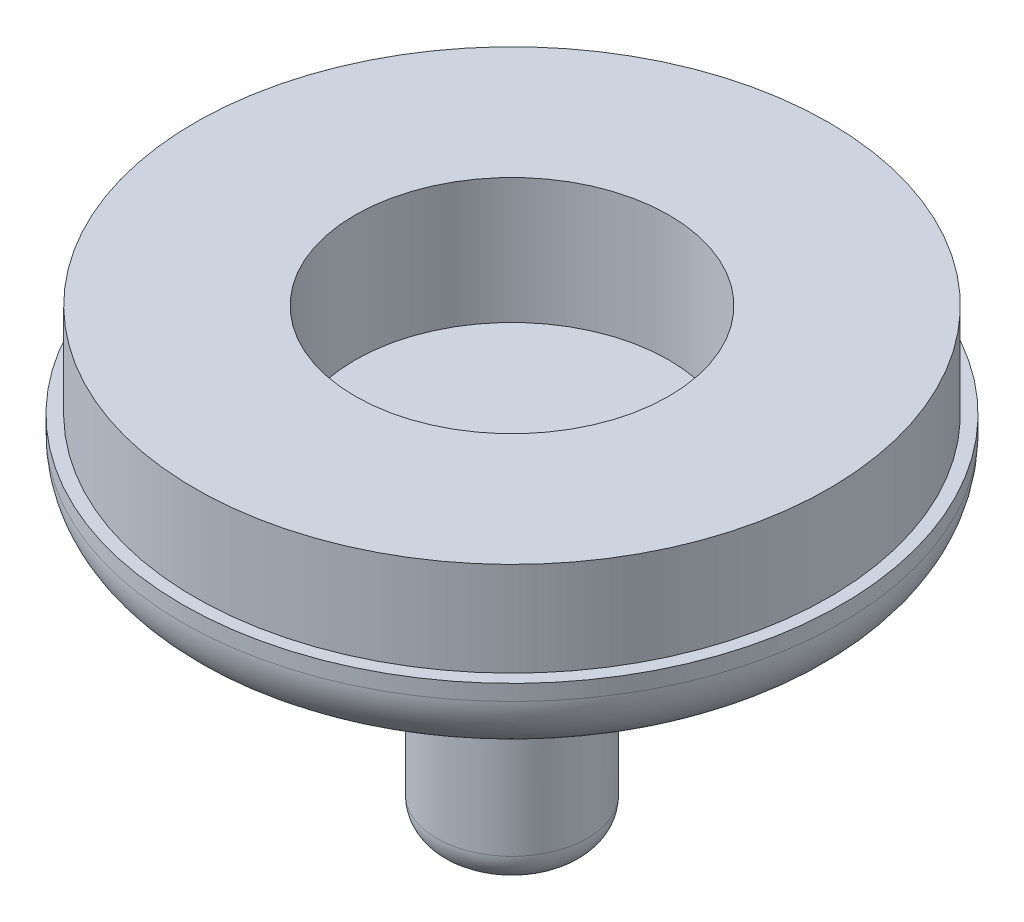
SolidWorks part; units mm, degrees
ref_plane "Front Plane" through (0, 0, 0) normal (0, 0, 1) x (1, 0, 0)
ref_plane "Top Plane" through (0, 0, 0) normal (0, 1, 0) x (1, 0, 0)
ref_plane "Right Plane" through (0, 0, 0) normal (1, 0, 0) x (0, 0, -1)
sketch "Sketch1" plane through (0, 0, 0) normal (0, 1, 0) x (1, 0, 0)
  circle A0 centre (0, 0) radius 13.335
extrude "Boss-Extrude1" add sketch "Sketch1" along normal blind 3.175 contours A0
sketch "Sketch2" plane through (0, 3.175, 0) normal (0, 1, 0) x (1, 0, 0)
  circle A0 centre (0, 0) radius 12.827
extrude "Boss-Extrude2" add sketch "Sketch2" along normal blind 3.81
sketch "Sketch3" plane through (0, 6.985, 0) normal (0, 1, 0) x (1, 0, 0)
  circle A0 centre (0, 0) radius 6.35
extrude "Cut-Extrude2" cut sketch "Sketch3" against normal blind 5.08
sketch "Sketch4" plane through (0, 6.985, 0) normal (0, 1, 0) x (1, 0, 0)
  circle A1 centre (9.525, 0) radius 1.5875
ref_axis "Axis1" through (0, 1.905, 0) along (0, 1, 0)
fillet "Fillet1" radius 2.54 1 edges at (0, 0, 13.335)
sketch "Sketch5" plane through (0, 0, 0) normal (0, -1, 0) x (1, 0, 0)
  circle A0 centre (0, 0) radius 3.048
extrude "Boss-Extrude3" add sketch "Sketch5" along normal blind 11.43
fillet "Fillet2" radius 1.27 1 edges at (0, -11.43, -3.048)
fillet "Fillet3" radius 1.27 1 edges at (0, 0, 3.048)
